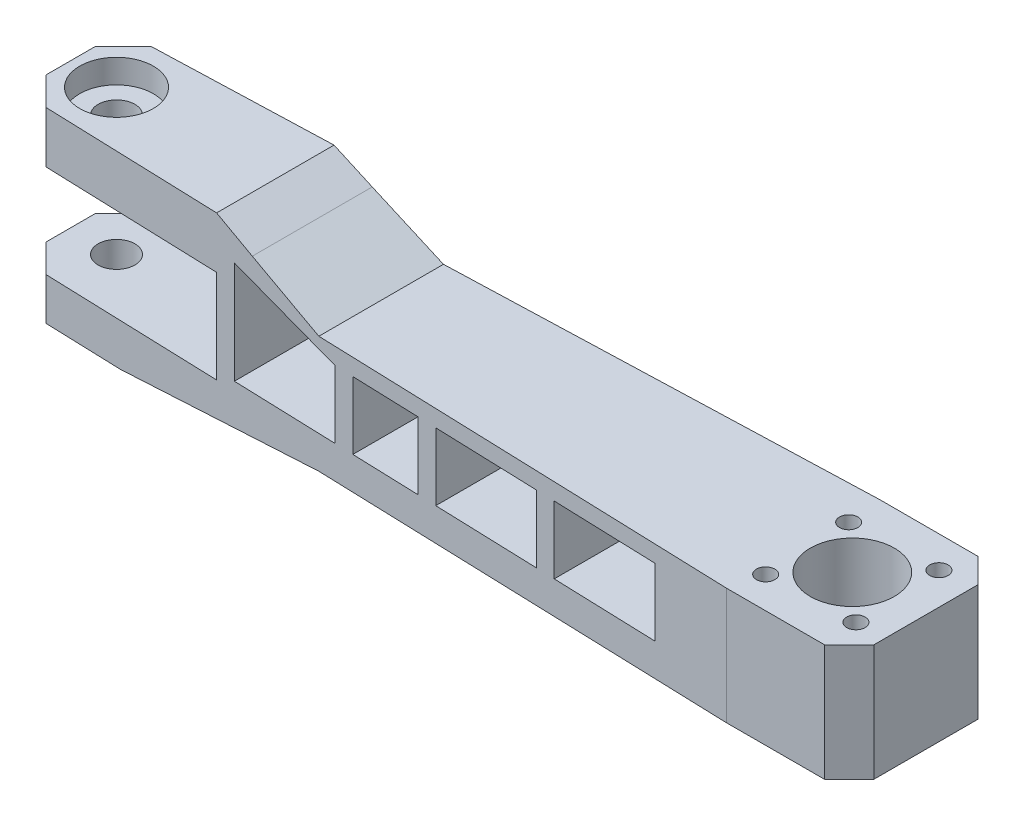
SolidWorks part; units mm, degrees
ref_plane "Front Plane" through (0, 0, 0) normal (0, 0, 1) x (1, 0, 0)
ref_plane "Top Plane" through (0, 0, 0) normal (0, 1, 0) x (1, 0, 0)
ref_plane "Right Plane" through (0, 0, 0) normal (1, 0, 0) x (0, 0, -1)
sketch "Sketch1" plane through (0, 0, 0) normal (0, 1, 0) x (1, 0, 0)
  line L0 (0, 0) -> (0, 47.3823) construction
  line L1 (0, 0) -> (-64.4031, 0) construction
  line L2 (0, 0) -> (79.7809, 0) construction
  line L3 (66.2432, 0) -> (83.7031, 18.9809) construction
  line L4 (78.2432, 8.5) -> (78.2432, -8.5)
  line L5 (78.2432, -8.5) -> (74.2409, -12.5022)
  line L6 (74.2409, -12.5022) -> (58.2409, -12.5022)
  line L7 (-61.2568, 4) -> (-61.2568, -4)
  line L8 (-61.2568, -4) -> (-56.6607, -8.5962)
  line L9 (-56.6607, -8.5962) -> (58.2409, -12.5022)
  line L10 (78.2432, 8.5) -> (74.2409, 12.5022)
  line L11 (74.2409, 12.5022) -> (58.2409, 12.5022)
  line L12 (-56.6607, 8.5962) -> (58.2409, 12.5022)
  line L13 (-61.2568, 4) -> (-56.6607, 8.5962)
  circle A0 centre (-53.7568, 0) radius 3
  circle A1 centre (66.2432, 0) radius 6.85
  circle A2 centre (-53.7568, 0) radius 6
  circle A3 centre (66.2432, 0) radius 7.8
  circle A4 centre (73.0132, 7.3598) radius 1.5
  circle A5 centre (73.6029, -6.77) radius 1.5
  circle A6 centre (59.4731, -7.3598) radius 1.5
  circle A7 centre (58.8834, 6.77) radius 1.5
  point P23 (66.2432, 0)
  point P29 (78.2432, 0)
  point P33 (-61.2568, 0)
  dimension "D1" = 120
  dimension "D2" = 12
  dimension "D3" = 6
  dimension "D4" = 13.7
  dimension "D5" = 15.6
  dimension "D6" = 10
  dimension "D7" = 132.61
  dimension "D9" = 12
  dimension "D10" = 8.5
  dimension "D11" = 135
  dimension "D12" = 5.66
  dimension "D13" = 16
  dimension "D14" = 135
  dimension "D15" = 7.5
  dimension "D16" = 4
  dimension "D17" = 135
  dimension "D18" = 6.5
  dimension "D8" = 4
extrude "Boss-Extrude1" add sketch "Sketch1" along normal blind 30.5 contours L13 L7 L8 L9 L6 L5 L4 L10 L11 L12 A7 A6 A5 A4 A3 A2 | A3 A1 | A2 A0 region at (11.9819, 0, 0) region at (-59.5871, 0, 0) region at (58.6638, 0, 0)
extrude "Cut-Extrude1" cut sketch "Sketch1<3>" against normal blind 3.9 from offset 30.5 contours A2
sketch "Sketch1<3>" plane through (0, 0, 0) normal (0, 1, 0) x (1, 0, 0) same geometry as "Sketch1"
extrude "Cut-Extrude2" cut sketch "Sketch1<4>" along normal mid plane 1.5 contours A3
sketch "Sketch1<4>" plane through (0, 0, 0) normal (0, 1, 0) x (1, 0, 0) same geometry as "Sketch1"
extrude "Cut-Extrude3" cut sketch "Sketch1<5>" against normal blind 1.5 from offset 30.5 contours A3
sketch "Sketch1<5>" plane through (0, 0, 0) normal (0, 1, 0) x (1, 0, 0) same geometry as "Sketch1"
sketch "Sketch3" plane through (0, 0, 0) normal (0, 0, 1) x (1, 0, 0)
  line L0 (-61.2568, 15.25) -> (78.2432, 15.25) construction
  line L1 (-61.2568, 30.5) -> (-61.2568, 0) construction
  line L2 (78.2432, 30.5) -> (78.2432, 0) construction
  line L3 (78.2432, 30.5) -> (78.2432, 3)
  line L4 (-61.2568, 30.5) -> (-61.2568, 22.1)
  line L5 (-61.2568, 0) -> (-61.2568, 6.9)
  line L7 (78.2432, 3) -> (78.2432, 22)
  line L8 (78.2432, 22) -> (78.2432, 3)
  line L9 (-61.2568, 30.5) -> (-27.8568, 30.5)
  line L10 (-56.6607, 30.5) -> (58.2409, 30.5) construction
  line L11 (-60.4805, 0) -> (-44.0805, 0)
  line L12 (-61.2568, 0) -> (-56.6607, 0) construction
  line L13 (-56.6607, 0) -> (58.2409, 0) construction
  line L14 (-61.2568, 22.1) -> (-27.8568, 22.1)
  line L15 (-27.8568, 22.1) -> (-27.8568, 6.9)
  line L16 (-27.8568, 6.9) -> (-61.2568, 6.9)
  line L17 (-61.2568, 22.1) -> (-61.2568, 6.9)
  line L18 (78.2432, 22) -> (-10.5968, 22)
  line L19 (-21.8319, 27.5) -> (-10.5968, 22)
  line L20 (-27.8568, 30.5) -> (-21.8319, 27.5)
  line L21 (-44.0805, 0) -> (-10.5968, 2.9294)
  line L22 (78.2432, 3) -> (-10.5968, 2.9294)
  line L23 (-27.8568, 30.5) -> (39.4474, 56.9362)
  line L24 (39.4474, 56.9362) -> (78.2432, 30.5)
  line L25 (-44.0805, 0) -> (9.3742, -19.7337)
  line L26 (9.3742, -19.7337) -> (78.2432, 0)
  line L27 (78.2432, 0) -> (78.2432, 3)
  dimension "D4" = 19
  dimension "D1" = 8.4
  dimension "D2" = 6.9
  dimension "D3" = 8.5
  dimension "D5" = 33.4
  dimension "D6" = 16.4
  dimension "D7" = 175
  dimension "D8" = 153.53
  dimension "D9" = 88.84
  dimension "D10" = 88.84
extrude "Cut-Extrude4" cut sketch "Sketch3" against normal mid plane 50 contours L0 L17 L16 L15 | L17 L0 L15 L14 | L26 L27 L22 L21 L25 | L24 L23 L20 L19 L18 L3 region at (-44.5568, 18.675, 0) region at (16.7196, -4.9368, 0) region at (-44.5568, 11.075, 0) region at (29.7289, 34.5068, 0)
sketch "Sketch4" plane through (0, 0, 0) normal (0, 0, 1) x (1, 0, 0)
  line L0 (-27.8568, 8.276) -> (58.2409, 8.276) construction
  line L1 (-27.8568, 6.9) -> (-27.8568, 22.1) construction
  line L2 (58.2409, 22) -> (58.2409, 2.9841) construction
  line L3 (-27.8568, 19.276) -> (58.2409, 19.276) construction
  line L4 (-24.8568, 8.276) -> (-24.8568, 24.9915)
  line L5 (-24.8568, 24.9915) -> (-7.8568, 19.276)
  line L6 (-7.8568, 19.276) -> (-7.8568, 8.276)
  line L7 (-7.8568, 8.276) -> (-24.8568, 8.276)
  line L8 (-4.8568, 19.276) -> (6.1432, 19.276)
  line L9 (6.1432, 19.276) -> (6.1432, 8.276)
  line L10 (6.1432, 8.276) -> (-4.8568, 8.276)
  line L11 (-4.8568, 8.276) -> (-4.8568, 19.276)
  line L12 (10.4665, 19.276) -> (26.1432, 19.276)
  line L13 (26.1432, 19.276) -> (26.1432, 8.276)
  line L14 (26.1432, 8.276) -> (9.1432, 8.276)
  line L15 (9.1432, 8.276) -> (9.1432, 19.276)
  line L16 (9.1432, 19.276) -> (10.4665, 19.276)
  line L17 (29.1432, 19.276) -> (46.1432, 19.276)
  line L18 (46.1432, 19.276) -> (46.1432, 8.276)
  line L19 (46.1432, 8.276) -> (29.1432, 8.276)
  line L20 (29.1432, 8.276) -> (29.1432, 19.276)
  dimension "D1" = 11
  dimension "D2" = 11
  dimension "D3" = 17
  dimension "D4" = 11
  dimension "D5" = 17
  dimension "D6" = 17
  dimension "D7" = 3
  dimension "D8" = 3
  dimension "D9" = 3
  dimension "D10" = 3
extrude "Cut-Extrude5" cut sketch "Sketch4" against normal mid plane 50 contours L7 L6 L5 L4 | L11 L10 L9 L8 | L16 L15 L14 L13 L12 region at (-16.9411, 15.3031, 0) region at (0.6432, 13.776, 0) region at (17.6432, 13.776, 0)
extrude "Cut-Extrude6" cut sketch "Sketch4<3>" against normal blind 30 from offset 20 contours L20 L19 L18 L17 region at (37.6432, 13.776, 0)
sketch "Sketch4<3>" plane through (0, 0, 0) normal (0, 0, 1) x (1, 0, 0) same geometry as "Sketch4"
